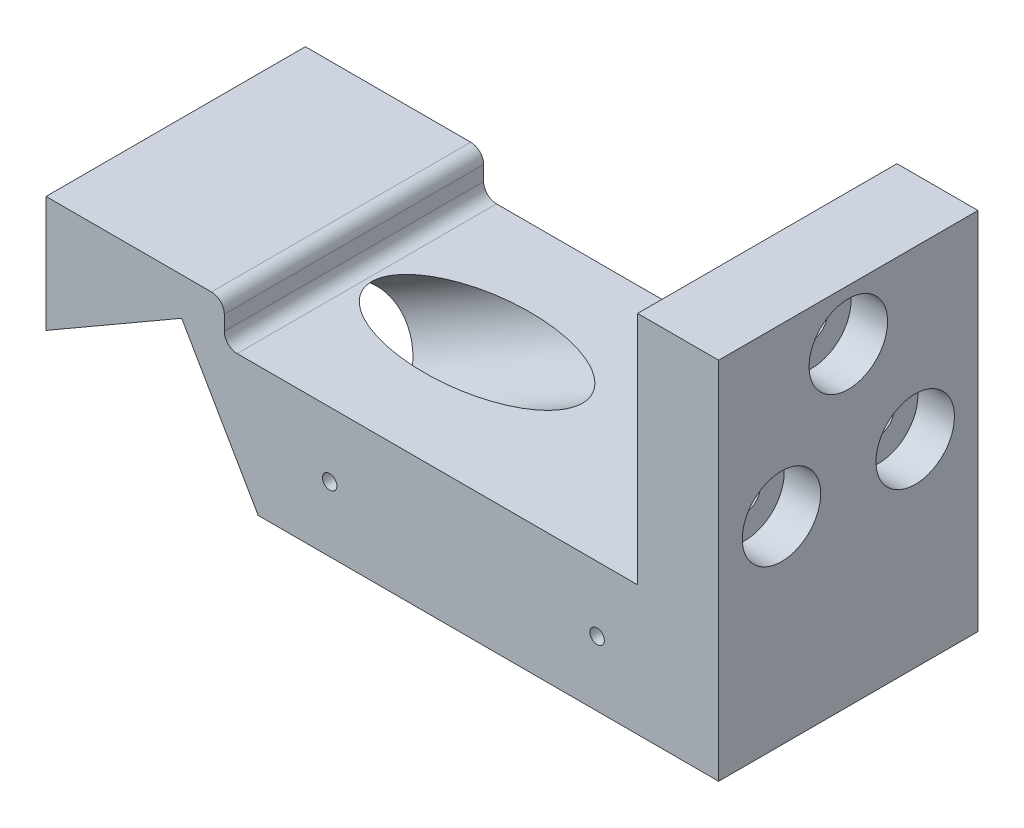
SolidWorks part; units mm, degrees
material "6061-T4 (SS)"
ref_plane "Front Plane" through (0, 0, 0) normal (0, 0, 1) x (1, 0, 0)
ref_plane "Top Plane" through (0, 0, 0) normal (0, 1, 0) x (1, 0, 0)
ref_plane "Right Plane" through (0, 0, 0) normal (1, 0, 0) x (0, 0, -1)
sketch "Sketch1" plane through (0, 0, 0) normal (0, 1, 0) x (1, 0, 0)
  line L1 (-36.5, 16) -> (36.5, 16)
  line L2 (-36.5, 16) -> (-36.5, -16)
  line L3 (-36.5, -16) -> (36.5, -16)
  line L4 (36.5, 16) -> (36.5, -16)
  line L5 (-36.5, 16) -> (36.5, -16) construction
  line L6 (-36.5, -16) -> (36.5, 16) construction
  point P0 (0, 0)
  dimension "D1" = 73
  dimension "D2" = 32
extrude "Boss-Extrude1" add sketch "Sketch1" along normal blind 16
sketch "Sketch78" plane through (0, 0, 16) normal (0, 0, 1) x (1, 0, 0)
  line L0 (-14.5, 16) -> (-12.9125, 16)
  line L1 (-36.5, 16) -> (-14.5, 16)
  line L2 (-36.5, 16) -> (-36.5, 21)
  line L3 (-36.5, 21) -> (-16.0875, 21)
  line L4 (-14.5, 17.5875) -> (-14.5, 19.4125)
  line L5 (-36.5, 16) -> (36.5, 16) construction
  line L6 (-12.9125, 16) -> (-12.9125, 17.5875) construction
  line L7 (-12.9125, 17.5875) -> (-14.5, 17.5875) construction
  arc A0 (-16.0875, 21) -> (-14.5, 19.4125) centre (-16.0875, 19.4125) cw
  arc A1 (-12.9125, 16) -> (-14.5, 17.5875) centre (-12.9125, 17.5875) cw
  dimension "D3" = 1.5875
  dimension "D1" = 5
  dimension "D2" = 22
  dimension "D4" = 1.5875
  dimension "D5" = 1.5875
extrude "Boss-Extrude4" add sketch "Sketch78" against normal up to surface (32 mm away) up to face at (0, 8, -16)
sketch "Sketch79" plane through (0, 0, -16) normal (0, 0, -1) x (-1, 0, 0)
  line L0 (-32.5, 1.97) -> (23.61, 1.97) construction
  line L1 (-32.5, 1.97) -> (-32.5, 29.2) construction
  line L2 (23.61, 1.97) -> (-20.8992, 27.6674) construction
  line L3 (33.135, 1.97) -> (34.135, 1.97) construction
  line L4 (14.4951, 7.2325) -> (19.7576, 16.3474)
  line L5 (19.7576, 16.3474) -> (36.5, 6.6812)
  line L6 (36.5, 21) -> (36.5, 0) construction
  line L7 (14.4951, 7.2325) -> (10.3194, 0)
  line L8 (-36.5, 0) -> (36.5, 0) construction
  line L9 (10.3194, 0) -> (36.5, 0)
  line L10 (36.5, 0) -> (36.5, 6.6812)
  circle A0 centre (23.61, 1.97) radius 9.525 construction
  circle A1 centre (23.61, 1.97) radius 10.525 construction
  dimension "D4" = 19.05
  dimension "D1" = 27.23
  dimension "D2" = 56.11
  dimension "D3" = 30
  dimension "D5" = 1
extrude "Cut-Extrude23" cut sketch "Sketch79" against normal blind 41
sketch "Sketch26" plane through (0, 0, 0) normal (0, -1, 0) x (1, 0, 0)
  line L0 (-10.3194, 16) -> (36.5, 16) construction
  line L1 (36.5, -16) -> (46.5, -16)
  line L2 (36.5, -16) -> (36.5, 16)
  line L3 (36.5, 16) -> (46.5, 16)
  line L4 (46.5, -16) -> (46.5, 16)
  dimension "D1" = 10
extrude "Boss-Extrude2" add sketch "Sketch26" against normal blind 45
sketch "Sketch15" plane through (-36.5, 0, 0) normal (-1, 0, 0) x (0, 0, 1)
  line L0 (-10, 14.6812) -> (10, 14.6812) construction
  line L1 (-10, 14.6812) -> (-16, 14.6812) construction
  line L3 (10, 14.6812) -> (16, 14.6812) construction
  line L6 (16, 21) -> (16, 6.6812) construction
  line L7 (-16, 21) -> (-16, 6.6812) construction
  line L9 (16, 6.6812) -> (-16, 6.6812) construction
  point P6 (0, 0)
  point P8 (0, 0)
  point P11 (0, 0)
  point P13 (0, 0)
  dimension "D3" = 20
  dimension "D4" = 8
sketch "Sketch14" plane through (-13.4261, 5.3809, -20) normal (-0.866, -0.5, 0) x (0, 0, 1)
  line L0 (4, 2.138) -> (20, 2.138) construction
  line L1 (20, 2.138) -> (36, 2.138) construction
  line L2 (36, 12.663) -> (36, -6.2133) construction
  line L3 (4, 12.663) -> (4, -6.2133) construction
  circle A0 centre (20, 2.138) radius 6.5
  point P3 (0, 0)
  point P5 (0, 0)
  point P8 (0, 0)
  point P9 (0, 0)
  point P12 (0, 0)
  point P13 (0, 0)
  dimension "D1" = 13
extrude "Cut-Extrude2" cut sketch "Sketch14" against normal blind 33 and the other way blind 41
sketch "Sketch27" plane through (46.5, 0, 0) normal (1, 0, 0) x (0, 0, -1)
  line L0 (16, 45) -> (-16, 45) construction
  line L1 (16, 45) -> (16, 0) construction
  line L3 (-8.2489, 24.4375) -> (8.2489, 24.4375) construction
  line L4 (0, 24.4375) -> (0, 38.725) construction
  line L5 (-8.2489, 24.4375) -> (-16, 24.4375) construction
  line L7 (8.2489, 24.4375) -> (16, 24.4375) construction
  line L9 (-16, 45) -> (-16, 0) construction
  circle A0 centre (0, 38.725) radius 1.595
  circle A1 centre (8.2489, 24.4375) radius 1.595
  circle A2 centre (-8.2489, 24.4375) radius 1.595
  point P8 (0, 0)
  point P11 (0, 0)
  point P18 (0, 0)
  dimension "D1" = 3.19
  dimension "D2" = 3.19
  dimension "D3" = 3.19
  dimension "D6" = 14.2875
  dimension "D7" = 16.4978
  dimension "D8" = 6.275
extrude "Cut-Extrude7" cut sketch "Sketch27" against normal through all
hole_wizard "#2-56 Tapped Hole1" positions "Sketch80" profile "Sketch81" tap size "#2-56" standard "ANSI Inch"
sketch "Sketch80" plane through (-36.5, 0, 0) normal (-1, 0, 0) x (0, 0, 1)
  point P0 (-10, 14.6812)
  point P3 (10, 14.6812)
  point P7 (0, 0)
  point P8 (-10, 14.6812)
sketch "Sketch81" plane through (-36.5, 14.6812, -10) normal (0, 1, 0) x (0, 0, 1)
  line L0 (0, 0) -> (0, 6.8842)
  line L1 (0, 6.8842) -> (0.889, 6.35)
  line L2 (0.889, 6.35) -> (0.889, 0)
  line L5 (0.889, 0) -> (0, 0)
  line L10 (0, 6.8842) -> (-0.889, 6.35) construction
  line L11 (0, -6.35) -> (0, 107.95) construction
  dimension "Tap Drill Dia." = 1.778
  dimension "Tap Drill Depth" = 6.35
  dimension "Drill Angle" = 118
hole_wizard "CBORE for #6 Socket Head Cap Screw1" positions "Sketch57" profile "Sketch58" counterbore size "#6" standard "ANSI Inch"
sketch "Sketch57" plane through (46.5, 0, 0) normal (1, 0, 0) x (0, 0, -1)
  point P0 (0, 38.725)
  point P3 (8.2489, 24.4375)
  point P6 (-8.2489, 24.4375)
sketch "Sketch58" plane through (46.5, 38.725, 0) normal (0, 1, 0) x (0, 0, -1)
  line L0 (0, 0) -> (0, 47.6408)
  line L1 (0, 47.6408) -> (1.8986, 46.5)
  line L2 (1.8986, 46.5) -> (1.8986, 4.5052)
  line L3 (1.8986, 4.5052) -> (4.8425, 4.5052)
  line L4 (4.8425, 4.5052) -> (4.8425, 0)
  line L5 (4.8425, 0) -> (0, 0)
  line L10 (0, 47.6408) -> (-1.8987, 46.5) construction
  line L11 (0, -6.35) -> (0, 107.95) construction
  dimension "Hole Dia." = 3.7973
  dimension "Hole Depth" = 46.5
  dimension "C'Bore Dia." = 9.685
  dimension "C'Bore Depth" = 4.5052
  dimension "Drill Angle" = 118
sketch "Sketch59" plane through (0, 0, -16) normal (0, 0, -1) x (-1, 0, 0)
  line L0 (36.5, 16) -> (36.5, 0) construction
  line L1 (36.5, 0) -> (-46.5, 0) construction
  line L2 (-46.5, 0) -> (-46.5, 16) construction
  line L3 (36.5, 21) -> (36.5, 6.6812) construction
  line L4 (-46.5, 16) -> (36.5, 16) construction
  line L5 (-46.5, 8) -> (36.5, 8) construction
  line L6 (-46.5, 45) -> (-46.5, 0) construction
  line L7 (-36.5, 16) -> (12.9125, 16) construction
  point P10 (-31.5, 8)
  point P11 (1.5, 8)
  point P12 (0, 0)
  point P13 (0, 0)
  point P14 (0, 0)
  point P15 (-46.5, 0)
  point P17 (0, 0)
  point P18 (36.5, 15.9867)
  dimension "D1" = 15
  dimension "D2" = 35
hole_wizard "#2-56 Tapped Hole2" positions "Sketch82" profile "Sketch83" tap size "#2-56" standard "ANSI Inch"
sketch "Sketch82" plane through (0, 0, -16) normal (0, 0, -1) x (-1, 0, 0)
  point P0 (-31.5, 8)
  point P3 (1.5, 8)
sketch "Sketch83" plane through (31.5, 8, -16) normal (1, 0, 0) x (0, 1, 0)
  line L0 (0, 0) -> (0, 6.8842)
  line L1 (0, 6.8842) -> (0.889, 6.35)
  line L2 (0.889, 6.35) -> (0.889, 0)
  line L5 (0.889, 0) -> (0, 0)
  line L10 (0, 6.8842) -> (-0.889, 6.35) construction
  line L11 (0, -6.35) -> (0, 107.95) construction
  dimension "Tap Drill Dia." = 1.778
  dimension "Tap Drill Depth" = 6.35
  dimension "Drill Angle" = 118
hole_wizard "#2-56 Tapped Hole3" positions "Sketch84" profile "Sketch85" tap size "#2-56" standard "ANSI Inch"
sketch "Sketch84" plane through (0, 0, 16) normal (0, 0, 1) x (1, 0, 0)
  point P0 (-1.5, 8)
  point P3 (31.5, 8)
sketch "Sketch85" plane through (-1.5, 8, 16) normal (1, 0, 0) x (0, -1, 0)
  line L0 (0, 0) -> (0, 6.8842)
  line L1 (0, 6.8842) -> (0.889, 6.35)
  line L2 (0.889, 6.35) -> (0.889, 0)
  line L5 (0.889, 0) -> (0, 0)
  line L10 (0, 6.8842) -> (-0.889, 6.35) construction
  line L11 (0, -6.35) -> (0, 107.95) construction
  dimension "Tap Drill Dia." = 1.778
  dimension "Tap Drill Depth" = 6.35
  dimension "Drill Angle" = 118
hole_wizard "#2-56 Tapped Hole4" positions "Sketch86" profile "Sketch87" tap size "#2-56" standard "ANSI Inch"
sketch "Sketch86" plane through (-7.7395, -4.4684, 0) normal (-0.866, -0.5, 0) x (0, 0, 1)
  line L0 (-10, 13.5111) -> (10, 13.5111) construction
  circle A1 centre (0, 13.5111) radius 6.5
  circle A2 centre (0, 13.5111) radius 6.5 construction
  point P0 (-10, 13.5111)
  point P2 (10, 13.5111)
  point P19 (0, 13.5111)
  point P32 (0, 0)
  dimension "D1" = 10
sketch "Sketch87" plane through (-14.4951, 7.2325, -10) normal (0, 0, 1) x (0.5, -0.866, 0)
  line L0 (0, 0) -> (0, 6.8842)
  line L1 (0, 6.8842) -> (0.889, 6.35)
  line L2 (0.889, 6.35) -> (0.889, 0)
  line L5 (0.889, 0) -> (0, 0)
  line L10 (0, 6.8842) -> (-0.889, 6.35) construction
  line L11 (0, -6.35) -> (0, 107.95) construction
  dimension "Tap Drill Dia." = 1.778
  dimension "Tap Drill Depth" = 6.35
  dimension "Drill Angle" = 118
